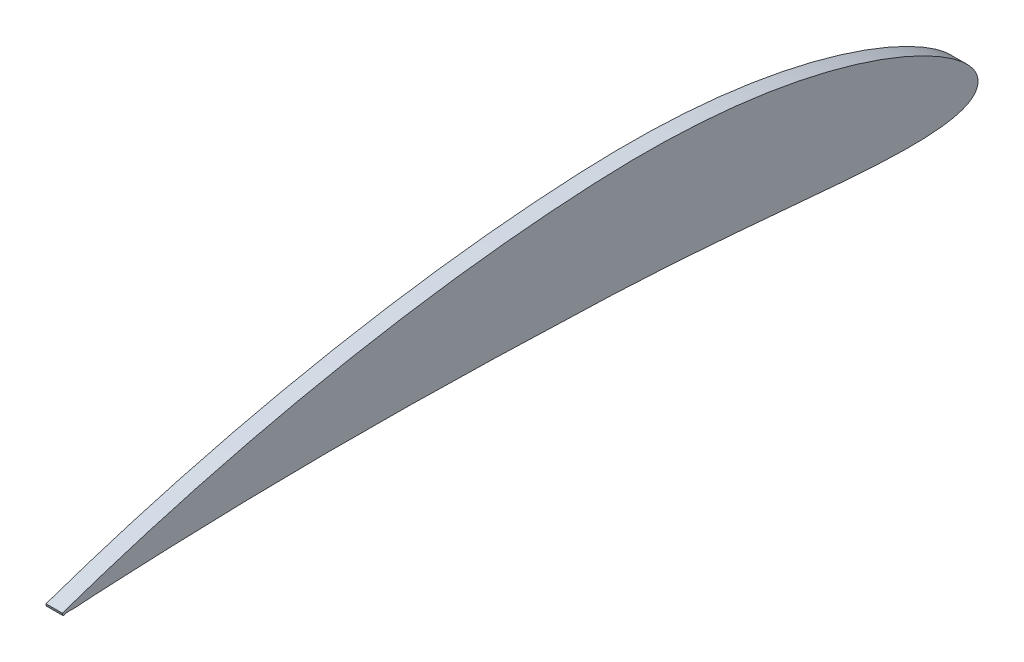
SolidWorks part; units mm, degrees
material "Balsa"
ref_plane "Front Plane" through (0, 0, 0) normal (0, 0, 1) x (1, 0, 0)
ref_plane "Top Plane" through (0, 0, 0) normal (0, 1, 0) x (1, 0, 0)
ref_plane "Right Plane" through (0, 0, 0) normal (1, 0, 0) x (0, 0, -1)
curve "Curve1"
  spline degree 3 poles (0, 0.0012, 1.0003) (0, 0.0015, 0.9994) (0, 0.0028, 0.9958) (0, 0.0055, 0.9879) (0, 0.0099, 0.9747) (0, 0.0159, 0.9565) (0, 0.0233, 0.9333) (0, 0.0318, 0.9054) (0, 0.0411, 0.8731) (0, 0.051, 0.8366) (0, 0.0612, 0.7964) (0, 0.0713, 0.7528) (0, 0.0811, 0.7063) (0, 0.0903, 0.6574) (0, 0.0985, 0.6067) (0, 0.1057, 0.5546) (0, 0.1115, 0.5018) (0, 0.1158, 0.4488) (0, 0.1186, 0.3959) (0, 0.1189, 0.3436) (0, 0.1164, 0.2927) (0, 0.1112, 0.2442) (0, 0.1037, 0.1988) (0, 0.0942, 0.157) (0, 0.0831, 0.1194) (0, 0.0711, 0.0865) (0, 0.0584, 0.0585) (0, 0.0457, 0.0357) (0, 0.0334, 0.0184) (0, 0.0218, 0.0064) (0, 0.0108, -0.0005) (0, -0.0003, -0.0011) (0, -0.0092, 0.0055) (0, -0.0148, 0.017) (0, -0.0185, 0.0329) (0, -0.0204, 0.0533) (0, -0.0208, 0.0781) (0, -0.0198, 0.107) (0, -0.0176, 0.1398) (0, -0.0147, 0.176) (0, -0.0111, 0.2153) (0, -0.0074, 0.2574) (0, -0.0037, 0.3019) (0, -0.0005, 0.3484) (0, 0.002, 0.397) (0, 0.0037, 0.4471) (0, 0.0055, 0.4983) (0, 0.0069, 0.5496) (0, 0.0079, 0.6006) (0, 0.0085, 0.6505) (0, 0.0086, 0.699) (0, 0.0083, 0.7455) (0, 0.0076, 0.7894) (0, 0.0065, 0.8302) (0, 0.0053, 0.8675) (0, 0.0039, 0.9007) (0, 0.0027, 0.9296) (0, 0.0013, 0.9539) (0, 0.0006, 0.9727) (0, -0.0011, 0.9872) (0, 0, 0.9944) (0, -0.002, 0.9999) (0, -0.0005, 1) (0, 0, 1) knots 0 0 0 0 0.001372 0.005465 0.012235 0.021602 0.033461 0.047671 0.064081 0.082496 0.102719 0.124527 0.147676 0.171913 0.196978 0.222597 0.248497 0.274385 0.300041 0.32569 0.350525 0.37428 0.396711 0.417577 0.436654 0.453744 0.46868 0.481329 0.491631 0.499616 0.505546 0.510185 0.514824 0.520702 0.528516 0.538466 0.550543 0.564643 0.580638 0.598345 0.617584 0.638174 0.659922 0.682632 0.706121 0.730727 0.7557 0.780732 0.805564 0.829932 0.85357 0.876213 0.89761 0.917519 0.935698 0.951943 0.966047 0.97784 0.987174 0.993932 0.998018 0.999386 1 1 1 1
sketch "Sketch1" plane through (0, 0, 0) normal (1, 0, 0) x (0, 0, -1)
  line L0 (-354.7873, -0.0303) -> (-354.8762, 0.4104)
  line L1 (-354.7873, -0.0303) -> (0.8093, 1.5275) construction
  line L2 (0.8093, 1.5275) -> (0.7921, 5.4415) construction
  spline S1 degree 3 poles (-354.8762, 0.4104) (-354.5599, 0.5194) (-353.2997, 0.9536) (-350.4787, 1.9271) (-345.801, 3.4978) (-336.0241, 6.7216) (-319.6545, 11.7989) (-300.5983, 17.1306) (-282.4229, 21.7243) (-261.1758, 26.6516) (-238.6223, 31.1455) (-208.7748, 36.0048) (-183.9617, 39.0905) (-158.9023, 41.1132) (-140.0967, 42.1114) (-121.5167, 42.2289) (-103.4222, 41.3211) (-86.1884, 39.4787) (-70.0435, 36.8105) (-55.1998, 33.4329) (-41.8434, 29.5109) (-30.1305, 25.2201) (-20.187, 20.7343) (-12.1072, 16.2263) (-5.9269, 11.8553) (-1.6792, 7.7165) (0.7658, 3.7968) (0.9875, -0.1483) (-1.3511, -3.3089) (-5.4508, -5.2881) (-11.0873, -6.5875) (-18.3491, -7.2685) (-27.1638, -7.4049) (-37.4471, -7.0538) (-49.0831, -6.3019) (-61.9524, -5.238) (-75.9299, -3.9839) (-96.4067, -2.1536) (-117.9372, -0.4584) (-140.4848, 0.6745) (-158.2965, 1.2867) (-176.4839, 1.9179) (-200.672, 2.5862) (-224.5411, 2.9791) (-247.8302, 3.0285) (-264.3373, 2.9074) (-279.9331, 2.6564) (-294.438, 2.2829) (-307.6819, 1.8521) (-319.5134, 1.3711) (-329.7674, 0.9129) (-338.3889, 0.4268) (-345.077, 0.1915) (-350.2276, -0.4064) (-352.7802, -0.0354) (-354.7446, -0.7581) (-354.7772, -0.2025) (-354.7873, -0.0303) knots 0 0 0 0 0.001372 0.005465 0.012235 0.021602 0.047671 0.082496 0.102719 0.124527 0.171913 0.196978 0.248497 0.274385 0.300041 0.32569 0.350525 0.37428 0.396711 0.417577 0.436654 0.453744 0.46868 0.481329 0.491631 0.499616 0.505546 0.510185 0.514824 0.520702 0.528516 0.538466 0.550543 0.564643 0.580638 0.598345 0.617584 0.638174 0.682632 0.706121 0.730727 0.7557 0.780732 0.829932 0.85357 0.876213 0.89761 0.917519 0.935698 0.951943 0.966047 0.97784 0.987174 0.993932 0.998018 0.999386 1 1 1 1
  dimension "D1" = 355.6
extrude "Boss-Extrude1" add sketch "Sketch1" along normal blind 3.175 and the other way blind 3.175
